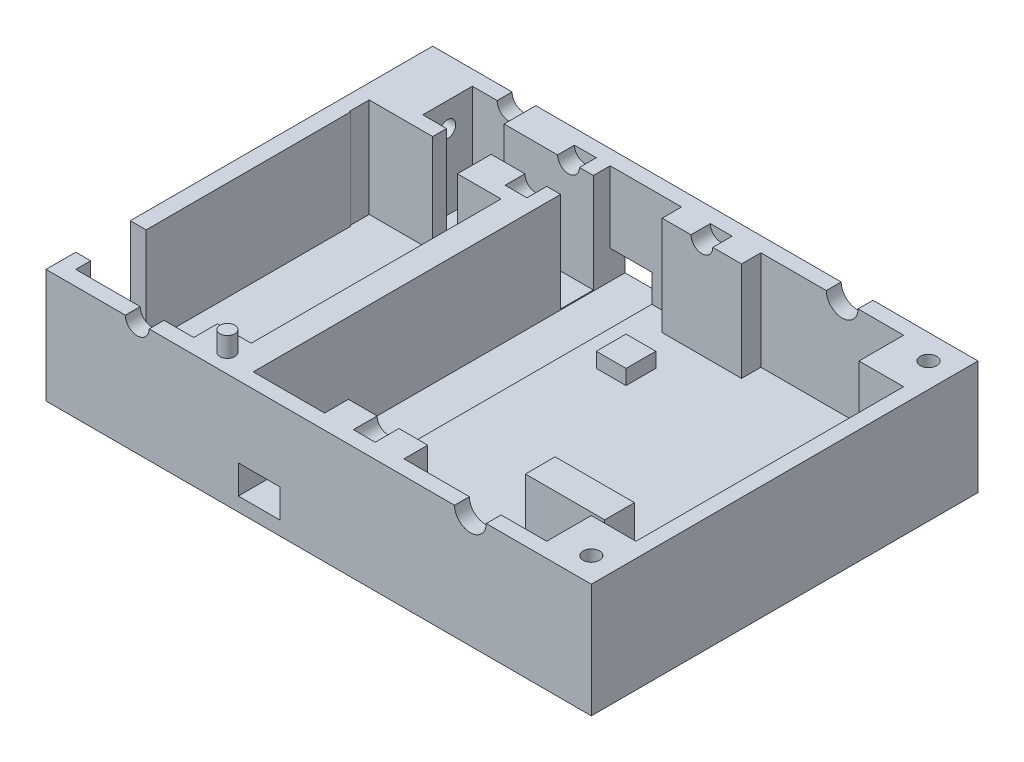
SolidWorks part; units mm, degrees
ref_plane "前视基准面" through (0, 0, 0) normal (0, 0, 1) x (1, 0, 0)
ref_plane "上视基准面" through (0, 0, 0) normal (0, 1, 0) x (1, 0, 0)
ref_plane "右视基准面" through (0, 0, 0) normal (1, 0, 0) x (0, 0, -1)
other "Configuration Table"
sketch "草图1" plane through (0, 0, 0) normal (0, 1, 0) x (1, 0, 0)
  line L1 (-27.5, 19.5) -> (27.5, 19.5)
  line L2 (-27.5, 19.5) -> (-27.5, -19.5)
  line L3 (-27.5, -19.5) -> (27.5, -19.5)
  line L4 (27.5, 19.5) -> (27.5, -19.5)
  line L5 (-27.5, 19.5) -> (27.5, -19.5) construction
  line L6 (-27.5, -19.5) -> (27.5, 19.5) construction
  point P0 (0, 0)
  dimension "D1" = 55
  dimension "D2" = 39
extrude "凸台-拉伸1" add sketch "草图1" along normal blind 11.5
shell "抽壳1" thickness 1.5 removed face at (0, 11.5, 0)
sketch "草图2" plane through (0, 0, -19.5) normal (0, 0, -1) x (-1, 0, 0)
  line L0 (7.9, 1.6) -> (4.1, 1.6) construction
  line L1 (3.9, 4.3) -> (8.1, 4.3)
  line L2 (3.9, 4.3) -> (3.9, 1.4)
  line L3 (3.9, 1.4) -> (8.1, 1.4)
  line L4 (8.1, 4.3) -> (8.1, 1.4)
  line L5 (7.9, 1.6) -> (7.9, 4.1) construction
  line L6 (7.9, 4.1) -> (4.1, 4.1) construction
  line L7 (4.1, 1.6) -> (4.1, 4.1) construction
  circle A0 centre (-15.3, 11.5) radius 1.6
  circle A1 centre (18.3, 11.5) radius 1.2
  circle A2 centre (-15.3, 11.5) radius 1.5 construction
  circle A3 centre (18.3, 11.5) radius 1 construction
  dimension "D1" = 0.1
  dimension "D2" = 0.2
  dimension "D3" = 0.2
  dimension "D4" = 0.2
  dimension "D5" = 0.2
  dimension "D6" = 0.2
extrude "切除-拉伸1" cut sketch "草图2" against normal through all
sketch "草图3" plane through (0, 1.5, 0) normal (0, 1, 0) x (1, 0, 0)
  line L0 (-25.8, -15.5) -> (-10.8, -15.5) construction
  line L5 (-10.7, 9.6) -> (-10.7, -15.6)
  line L6 (-15.1, 13) -> (-8.1, 13)
  line L7 (-15.1, 13) -> (-15.1, 9.6)
  line L8 (-15.1, 9.6) -> (-10.7, 9.6)
  line L10 (-17.1, -18) -> (13.7, -18) construction
  line L11 (-10.7, -18) -> (-8.1, -18)
  line L13 (-14.3, -17.8) -> (-14.3, -15.5) construction
  line L14 (-28.8, -11) -> (-25.8, -11) construction
  line L15 (-26, 9.6) -> (-25.9, 9.6)
  line L16 (-15.3, 9.5) -> (-15.3, 11.5) construction
  line L17 (-10.8, 9.5) -> (-10.8, -15.5) construction
  line L18 (-8.1, 18) -> (-8.1, -18) construction
  line L19 (13.7, 18) -> (-17.1, 18) construction
  line L20 (-17.1, 18) -> (-8.1, 18)
  line L21 (-17.1, 18) -> (-17.1, 16.3)
  line L22 (-17.1, 16.3) -> (-8.1, 16.3)
  line L23 (-8.1, 18) -> (-8.1, 16.3)
  line L24 (-17.1, 18) -> (-17.1, 19.5) construction
  line L25 (-8.1, 13) -> (-8.1, -18)
  line L26 (4.6159, 15.85) -> (4.2435, 15.85) construction
  line L27 (-0.9, 18) -> (7.1, 18)
  line L28 (-0.9, 18) -> (-0.9, 16.05)
  line L29 (-0.9, 16.05) -> (7.1, 16.05)
  line L30 (7.1, 18) -> (7.1, 16.05)
  line L31 (4.1, -18.1452) -> (4.1, 18.1548) construction
  line L32 (-17.1, -18) -> (13.7, -18) construction
  line L33 (-0.9, -15.6) -> (7.1, -15.6)
  line L34 (-0.9, -15.6) -> (-0.9, -18)
  line L35 (-0.9, -18) -> (7.1, -18)
  line L36 (7.1, -15.6) -> (7.1, -18)
  line L37 (-26, 9.6) -> (-26, -11)
  line L38 (26, 18) -> (16.9, 18) construction
  line L39 (21.5, 18) -> (26, 18)
  line L40 (21.5, 18) -> (21.5, 13.5)
  line L41 (21.5, 13.5) -> (26, 13.5)
  line L42 (26, 18) -> (26, 13.5)
  line L43 (26, -18) -> (26, 18) construction
  line L44 (-26, 18) -> (-26, -18) construction
  line L45 (21.5, -13.5) -> (26, -13.5)
  line L46 (21.5, -13.5) -> (21.5, -18)
  line L47 (21.5, -18) -> (26, -18)
  line L48 (26, -13.5) -> (26, -18)
  line L49 (-26, 18) -> (-22, 18)
  line L50 (-26, 18) -> (-26, 13)
  line L52 (-22, 18) -> (-22, 13)
  line L53 (-26, 11.6) -> (-19.6, 11.6)
  line L54 (-26, 11.6) -> (-26, 13)
  line L55 (-22, 13) -> (-19.6, 13)
  line L56 (-19.6, 11.6) -> (-19.6, 13)
  line L57 (-15.3, 11.5) -> (-21.3, 11.5) construction
  line L58 (-19.3, 19) -> (-19.3, 11.5) construction
  line L59 (-10.8, 9.5) -> (-25.8, 9.5) construction
  line L60 (-19.5, 18) -> (-26, 18) construction
  line L61 (-26, -11) -> (-25.9, -11)
  line L62 (-14.1, -15.6) -> (-10.7, -15.6)
  line L63 (-14.1, -15.6) -> (-14.1, -18)
  line L64 (-14.1, -18) -> (-10.7, -18)
  line L65 (-25.9, 9.6) -> (-25.9, -11)
  dimension "D2" = 4
  dimension "D3" = 0.1
  dimension "D4" = 0.2
  dimension "D5" = 1.7
  dimension "D6" = 0.1
  dimension "D7" = 8
  dimension "D8" = 0.2
  dimension "D9" = 3
  dimension "D10" = 8
  dimension "D11" = 3
  dimension "D12" = 2.4
  dimension "D13" = 4.5
  dimension "D14" = 4.5
  dimension "D15" = 4.5
  dimension "D16" = 4.5
  dimension "D17" = 0.3
  dimension "D18" = 0.1
  dimension "D19" = 5
  dimension "D20" = 0.1
  dimension "D21" = 0.2
  dimension "D22" = 0.1
extrude "凸台-拉伸2" add sketch "草图3" along normal up to surface (10 mm away) up to face at (-23.125, 11.5, 0)
sketch "草图4" plane through (0, 0, 19.5) normal (0, 0, 1) x (1, 0, 0)
  circle A0 centre (3.1, 11.5) radius 1.1
  circle A1 centre (3.1, 11.5) radius 1 construction
  dimension "D1" = 0.1
extrude "切除-拉伸2" cut sketch "草图4" against normal offset from surface (36 mm away) 1.5 from offset 1.5 up to face at (-6, 2.85, -19.5) offset against normal yes
sketch "草图5" plane through (0, 0, -19.5) normal (0, 0, -1) x (-1, 0, 0)
  circle A0 centre (10.6, 11.5) radius 1.1
  circle A1 centre (10.6, 11.5) radius 1 construction
  dimension "D1" = 0.1
extrude "切除-拉伸3" cut sketch "草图5" against normal blind 7 from offset 1.5 offset against normal yes
sketch "草图6" plane through (0, 1.5, 0) normal (0, 1, 0) x (1, 0, 0)
  line L0 (-0.9, 18) -> (-8.1, 18) construction
  line L1 (-1.1, 12.6) -> (1.9, 12.6)
  line L2 (-1.1, 12.6) -> (-1.1, 9.6)
  line L3 (-1.1, 9.6) -> (1.9, 9.6)
  line L4 (1.9, 12.6) -> (1.9, 9.6)
  line L6 (-8.1, -18) -> (-8.1, 13) construction
  line L8 (-32, 4) -> (-27.5, 4)
  line L9 (-32, 4) -> (-32, -4)
  line L10 (-32, -4) -> (-27.5, -4)
  line L11 (-27.5, 4) -> (-27.5, -4)
  line L14 (-27.5, 0) -> (-45.462, 0) construction
  line L15 (-27.5, 19.5) -> (-27.5, -19.5) construction
  dimension "D1" = 8.4
  dimension "D2" = 3
  dimension "D3" = 3
  dimension "D4" = 7
  dimension "D5" = 4.5
  dimension "D6" = 8
extrude "变速卡位凸台-拉伸3" add sketch "草图6" along normal blind 1.5 and the other way blind 1.5
sketch "草图7" plane through (0, 0, 0) normal (0, -1, 0) x (1, 0, 0)
  line L0 (-32, -4) -> (-32, 4) construction
  line L1 (27.5, 0) -> (56.3628, 0) construction
  line L2 (27.5, 19.5) -> (27.5, -19.5) construction
  line L3 (21.5, 13.5) -> (21.5, 18) construction
  line L4 (26, 13.5) -> (21.5, 13.5) construction
  circle A0 centre (-29.8, 0) radius 1
  circle A1 centre (25, 17) radius 0.825
  circle A2 centre (25, -17) radius 0.825
  dimension "D1" = 2
  dimension "D2" = 2.2
  dimension "D3" = 1.65
  dimension "D4" = 3.5
  dimension "D5" = 3.5
extrude "盖子固定切除-拉伸4" cut sketch "草图7" against normal through all
sketch "草图8" plane through (0, 1.5, 0) normal (0, 1, 0) x (1, 0, 0)
  line L0 (27.5, 0) -> (45.6897, 0) construction
  line L1 (27.5, -19.5) -> (27.5, 19.5) construction
  line L2 (26, -13.5) -> (26, 13.5) construction
  line L3 (26, -13.5) -> (21.5, -13.5) construction
  circle A0 centre (23, 7.6) radius 1
  circle A1 centre (23, -10.5) radius 1
  dimension "D1" = 2
  dimension "D2" = 3
  dimension "D3" = 3
  dimension "D4" = 2
  dimension "D5" = 3
  dimension "D6" = 3
extrude "底部螺丝孔切除-拉伸5" cut sketch "草图8" against normal through all
sketch "草图9" plane through (-27.5, 0, 0) normal (-1, 0, 0) x (0, 0, 1)
  line L0 (-19.5, 11.5) -> (19.5, 11.5) construction
  line L1 (-18, 11.5) -> (-18, 1.5) construction
  circle A0 centre (-15.502, 9) radius 0.825
  dimension "D1" = 1.65
  dimension "D2" = 2.5
  dimension "D3" = 2.498
extrude "前螺丝孔切除-拉伸6" cut sketch "草图9" against normal up to next
sketch "草图10" plane through (0, 1.5, 0) normal (0, 1, 0) x (1, 0, 0)
  line L0 (16.8, -26.9936) -> (16.8, 34.2064) construction
  line L1 (11.55, -7.2) -> (19.55, -7.2)
  line L2 (11.55, -7.2) -> (11.55, -10.2)
  line L3 (11.55, -10.2) -> (19.55, -10.2)
  line L4 (19.55, -7.2) -> (19.55, -10.2)
  line L5 (16.0993, -7.1) -> (16.9803, -7.1) construction
  dimension "D1" = 8
  dimension "D2" = 2.75
  dimension "D3" = 0.1
  dimension "D4" = 3
extrude "3mm轴卡位凸台-拉伸4" add sketch "草图10" along normal blind 7
sketch "草图11" plane through (-27.5, 0, 0) normal (-1, 0, 0) x (0, 0, 1)
  line L1 (16.5, 3.5) -> (11, 3.5)
  line L2 (16.5, 3.5) -> (16.5, 11.5)
  line L3 (16.5, 11.5) -> (11, 11.5)
  line L4 (11, 3.5) -> (11, 11.5)
  line L5 (-19.5, 11.5) -> (19.5, 11.5) construction
  line L6 (11, 7.5) -> (11, 3.5) construction
extrude "切除-拉伸4" cut sketch "草图11" against normal up to next
sketch "草图12" plane through (0, 11.5, 0) normal (0, 1, 0) x (1, 0, 0)
  line L0 (-8.1, -18) -> (-8.1, 13) construction
  line L1 (-10.7, -15.6) -> (-14.1, -15.6) construction
  circle A0 centre (-11.1, -17.6) radius 0.75
  dimension "D1" = 1.5
  dimension "D2" = 3
  dimension "D3" = 2
extrude "凸台-拉伸5" add sketch "草图12" along normal blind 2
